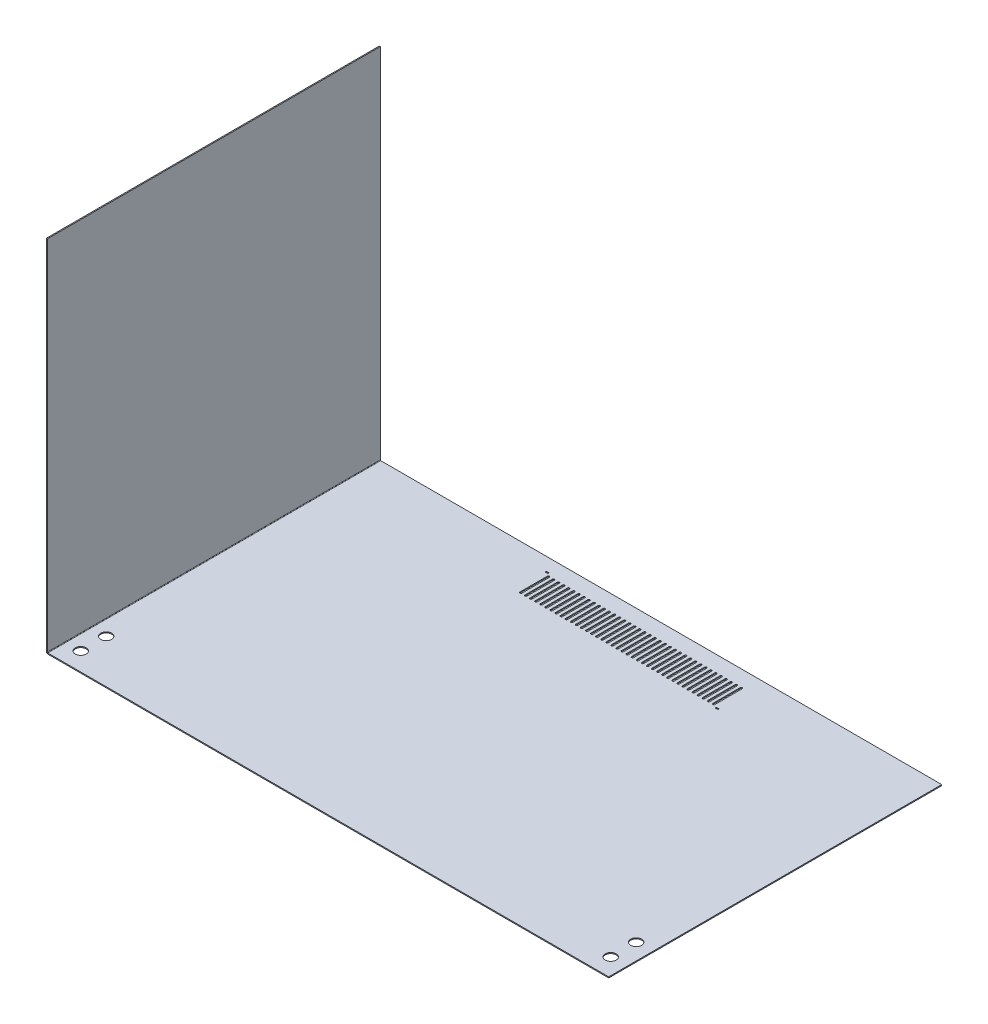
SolidWorks part; units mm, degrees
note: The reader was unsure of these and kept them because the rebuilt part matched: flange length of "Ребро-кромка1".
ref_plane "Спереди" through (0, 0, 0) normal (0, 0, 1) x (1, 0, 0)
ref_plane "Сверху" through (0, 0, 0) normal (0, 1, 0) x (1, 0, 0)
ref_plane "Справа" through (0, 0, 0) normal (1, 0, 0) x (0, 0, -1)
sketch "Эскиз1" plane through (0, 0, 0) normal (0, 1, 0) x (1, 0, 0)
  line L1 (0, 0) -> (1108, 0)
  line L2 (0, 0) -> (0, 656)
  line L3 (0, 656) -> (1108, 656)
  line L4 (1108, 0) -> (1108, 656)
  dimension "D1" = 656
  dimension "D2" = 1108
base flange "Базовая кромка1" sketch "Эскиз1" thickness 2 reverse thickness direction no parameters "D1"=1
edge flange "Ребро-кромка1" sketch "Эскиз19" flange angle 90 flange length 708 flange position material inside bend radius 1 thickness 2 relief rectangular parameters "D6"=10
bend "EdgeBend5" bend radius 1 bend angle 90 parameters "D5"=1
sketch "Эскиз19" plane through (0, 0, 0) normal (-1, 0, 0) x (0, 0, 1)
  line L0 (-656, 0) -> (0, 0) construction
  line L1 (-656, 0) -> (0, 0)
  line L2 (-656, 0) -> (-656, 706)
  line L3 (-656, 706) -> (0, 706)
  line L4 (0, 706) -> (0, 0)
sketch "Эскиз21" plane through (0, -2, 0) normal (0, -1, 0) x (1, 0, 0)
  line L0 (554, 0) -> (554, -656) construction
  line L1 (0, 0) -> (1108, 0) construction
  line L2 (1108, -656) -> (3, -656) construction
  line L3 (0, 0) -> (0, -656) construction
  line L4 (3, 0) -> (1108, 0) construction
  line L5 (746, -623) -> (746, -569) construction
  line L10 (744, -623) -> (744, -569)
  line L11 (748, -623) -> (748, -569)
  line L12 (554, -626) -> (554, -566) construction
  line L13 (746, -566) -> (362, -566) construction
  line L14 (749, -569) -> (749, -623) construction
  line L15 (746, -626) -> (362, -626) construction
  line L16 (359, -569) -> (359, -623) construction
  line L17 (736, -623) -> (736, -569) construction
  line L18 (734, -623) -> (734, -569)
  line L19 (738, -623) -> (738, -569)
  line L20 (726, -623) -> (726, -569) construction
  line L21 (724, -623) -> (724, -569)
  line L22 (728, -623) -> (728, -569)
  line L23 (716, -623) -> (716, -569) construction
  line L24 (714, -623) -> (714, -569)
  line L25 (718, -623) -> (718, -569)
  line L26 (706, -623) -> (706, -569) construction
  line L27 (704, -623) -> (704, -569)
  line L28 (708, -623) -> (708, -569)
  line L29 (696, -623) -> (696, -569) construction
  line L30 (694, -623) -> (694, -569)
  line L31 (698, -623) -> (698, -569)
  line L32 (686, -623) -> (686, -569) construction
  line L33 (684, -623) -> (684, -569)
  line L34 (688, -623) -> (688, -569)
  line L35 (676, -623) -> (676, -569) construction
  line L36 (674, -623) -> (674, -569)
  line L37 (678, -623) -> (678, -569)
  line L38 (666, -623) -> (666, -569) construction
  line L39 (664, -623) -> (664, -569)
  line L40 (668, -623) -> (668, -569)
  line L41 (656, -623) -> (656, -569) construction
  line L42 (654, -623) -> (654, -569)
  line L43 (658, -623) -> (658, -569)
  line L44 (646, -623) -> (646, -569) construction
  line L45 (644, -623) -> (644, -569)
  line L46 (648, -623) -> (648, -569)
  line L47 (636, -623) -> (636, -569) construction
  line L48 (634, -623) -> (634, -569)
  line L49 (638, -623) -> (638, -569)
  line L50 (626, -623) -> (626, -569) construction
  line L51 (624, -623) -> (624, -569)
  line L52 (628, -623) -> (628, -569)
  line L53 (616, -623) -> (616, -569) construction
  line L54 (614, -623) -> (614, -569)
  line L55 (618, -623) -> (618, -569)
  line L56 (606, -623) -> (606, -569) construction
  line L57 (604, -623) -> (604, -569)
  line L58 (608, -623) -> (608, -569)
  line L59 (596, -623) -> (596, -569) construction
  line L60 (594, -623) -> (594, -569)
  line L61 (598, -623) -> (598, -569)
  line L62 (586, -623) -> (586, -569) construction
  line L63 (584, -623) -> (584, -569)
  line L64 (588, -623) -> (588, -569)
  line L65 (576, -623) -> (576, -569) construction
  line L66 (574, -623) -> (574, -569)
  line L67 (578, -623) -> (578, -569)
  line L68 (566, -623) -> (566, -569) construction
  line L69 (564, -623) -> (564, -569)
  line L70 (568, -623) -> (568, -569)
  line L71 (556, -623) -> (556, -569) construction
  line L72 (554, -623) -> (554, -569)
  line L73 (558, -623) -> (558, -569)
  line L74 (546, -623) -> (546, -569) construction
  line L75 (544, -623) -> (544, -569)
  line L76 (548, -623) -> (548, -569)
  line L77 (536, -623) -> (536, -569) construction
  line L78 (534, -623) -> (534, -569)
  line L79 (538, -623) -> (538, -569)
  line L80 (526, -623) -> (526, -569) construction
  line L81 (524, -623) -> (524, -569)
  line L82 (528, -623) -> (528, -569)
  line L83 (516, -623) -> (516, -569) construction
  line L84 (514, -623) -> (514, -569)
  line L85 (518, -623) -> (518, -569)
  line L86 (506, -623) -> (506, -569) construction
  line L87 (504, -623) -> (504, -569)
  line L88 (508, -623) -> (508, -569)
  line L89 (496, -623) -> (496, -569) construction
  line L90 (494, -623) -> (494, -569)
  line L91 (498, -623) -> (498, -569)
  line L92 (486, -623) -> (486, -569) construction
  line L93 (484, -623) -> (484, -569)
  line L94 (488, -623) -> (488, -569)
  line L95 (476, -623) -> (476, -569) construction
  line L96 (474, -623) -> (474, -569)
  line L97 (478, -623) -> (478, -569)
  line L98 (466, -623) -> (466, -569) construction
  line L99 (464, -623) -> (464, -569)
  line L100 (468, -623) -> (468, -569)
  line L101 (456, -623) -> (456, -569) construction
  line L102 (454, -623) -> (454, -569)
  line L103 (458, -623) -> (458, -569)
  line L104 (446, -623) -> (446, -569) construction
  line L105 (444, -623) -> (444, -569)
  line L106 (448, -623) -> (448, -569)
  line L107 (436, -623) -> (436, -569) construction
  line L108 (434, -623) -> (434, -569)
  line L109 (438, -623) -> (438, -569)
  line L110 (426, -623) -> (426, -569) construction
  line L111 (424, -623) -> (424, -569)
  line L112 (428, -623) -> (428, -569)
  line L113 (416, -623) -> (416, -569) construction
  line L114 (414, -623) -> (414, -569)
  line L115 (418, -623) -> (418, -569)
  line L116 (406, -623) -> (406, -569) construction
  line L117 (404, -623) -> (404, -569)
  line L118 (408, -623) -> (408, -569)
  line L119 (396, -623) -> (396, -569) construction
  line L120 (394, -623) -> (394, -569)
  line L121 (398, -623) -> (398, -569)
  line L122 (386, -623) -> (386, -569) construction
  line L123 (384, -623) -> (384, -569)
  line L124 (388, -623) -> (388, -569)
  line L125 (376, -623) -> (376, -569) construction
  line L126 (374, -623) -> (374, -569)
  line L127 (378, -623) -> (378, -569)
  line L128 (366, -623) -> (366, -569) construction
  line L129 (364, -623) -> (364, -569)
  line L130 (368, -623) -> (368, -569)
  line L131 (357.4991, -630.0926) -> (357.5514, -628.5935) construction
  line L132 (358.9982, -630.1449) -> (356, -630.0402) construction
  line L133 (356.0523, -628.5411) -> (359.0505, -628.6458) construction
  line L134 (356.0253, -629.2906) -> (359.0253, -629.3954) construction
  line L135 (356.0671, -628.0914) -> (359.0671, -628.1961)
  line L136 (355.9834, -630.4899) -> (358.9834, -630.5947)
  line L137 (756.9969, -565.4955) -> (757.0492, -563.9964) construction
  line L138 (758.4959, -565.5478) -> (755.4978, -565.4431) construction
  line L139 (755.5501, -563.944) -> (758.5483, -564.0487) construction
  line L140 (755.523, -564.6935) -> (758.523, -564.7983) construction
  line L141 (755.5649, -563.4943) -> (758.5649, -563.599)
  line L142 (755.4812, -565.8928) -> (758.4812, -565.9976)
  circle A0 centre (32, -36) radius 10.75
  circle A1 centre (32, -86) radius 10.75
  circle A2 centre (1076, -86) radius 10.75
  circle A3 centre (1076, -36) radius 10.75
  arc A10 (362, -566) -> (359, -569) centre (362, -569) ccw construction
  arc A11 (359, -623) -> (362, -626) centre (362, -623) ccw construction
  arc A12 (746, -626) -> (749, -623) centre (746, -623) ccw construction
  arc A13 (749, -569) -> (746, -566) centre (746, -569) ccw construction
  arc A14 (744, -623) -> (748, -623) centre (746, -623) ccw
  arc A15 (748, -569) -> (744, -569) centre (746, -569) ccw
  arc A16 (734, -623) -> (738, -623) centre (736, -623) ccw
  arc A17 (738, -569) -> (734, -569) centre (736, -569) ccw
  arc A18 (724, -623) -> (728, -623) centre (726, -623) ccw
  arc A19 (728, -569) -> (724, -569) centre (726, -569) ccw
  arc A20 (714, -623) -> (718, -623) centre (716, -623) ccw
  arc A21 (718, -569) -> (714, -569) centre (716, -569) ccw
  arc A22 (704, -623) -> (708, -623) centre (706, -623) ccw
  arc A23 (708, -569) -> (704, -569) centre (706, -569) ccw
  arc A24 (694, -623) -> (698, -623) centre (696, -623) ccw
  arc A25 (698, -569) -> (694, -569) centre (696, -569) ccw
  arc A26 (684, -623) -> (688, -623) centre (686, -623) ccw
  arc A27 (688, -569) -> (684, -569) centre (686, -569) ccw
  arc A28 (674, -623) -> (678, -623) centre (676, -623) ccw
  arc A29 (678, -569) -> (674, -569) centre (676, -569) ccw
  arc A30 (664, -623) -> (668, -623) centre (666, -623) ccw
  arc A31 (668, -569) -> (664, -569) centre (666, -569) ccw
  arc A32 (654, -623) -> (658, -623) centre (656, -623) ccw
  arc A33 (658, -569) -> (654, -569) centre (656, -569) ccw
  arc A34 (644, -623) -> (648, -623) centre (646, -623) ccw
  arc A35 (648, -569) -> (644, -569) centre (646, -569) ccw
  arc A36 (634, -623) -> (638, -623) centre (636, -623) ccw
  arc A37 (638, -569) -> (634, -569) centre (636, -569) ccw
  arc A38 (624, -623) -> (628, -623) centre (626, -623) ccw
  arc A39 (628, -569) -> (624, -569) centre (626, -569) ccw
  arc A40 (614, -623) -> (618, -623) centre (616, -623) ccw
  arc A41 (618, -569) -> (614, -569) centre (616, -569) ccw
  arc A42 (604, -623) -> (608, -623) centre (606, -623) ccw
  arc A43 (608, -569) -> (604, -569) centre (606, -569) ccw
  arc A44 (594, -623) -> (598, -623) centre (596, -623) ccw
  arc A45 (598, -569) -> (594, -569) centre (596, -569) ccw
  arc A46 (584, -623) -> (588, -623) centre (586, -623) ccw
  arc A47 (588, -569) -> (584, -569) centre (586, -569) ccw
  arc A48 (574, -623) -> (578, -623) centre (576, -623) ccw
  arc A49 (578, -569) -> (574, -569) centre (576, -569) ccw
  arc A50 (564, -623) -> (568, -623) centre (566, -623) ccw
  arc A51 (568, -569) -> (564, -569) centre (566, -569) ccw
  arc A52 (554, -623) -> (558, -623) centre (556, -623) ccw
  arc A53 (558, -569) -> (554, -569) centre (556, -569) ccw
  arc A54 (544, -623) -> (548, -623) centre (546, -623) ccw
  arc A55 (548, -569) -> (544, -569) centre (546, -569) ccw
  arc A56 (534, -623) -> (538, -623) centre (536, -623) ccw
  arc A57 (538, -569) -> (534, -569) centre (536, -569) ccw
  arc A58 (524, -623) -> (528, -623) centre (526, -623) ccw
  arc A59 (528, -569) -> (524, -569) centre (526, -569) ccw
  arc A60 (514, -623) -> (518, -623) centre (516, -623) ccw
  arc A61 (518, -569) -> (514, -569) centre (516, -569) ccw
  arc A62 (504, -623) -> (508, -623) centre (506, -623) ccw
  arc A63 (508, -569) -> (504, -569) centre (506, -569) ccw
  arc A64 (494, -623) -> (498, -623) centre (496, -623) ccw
  arc A65 (498, -569) -> (494, -569) centre (496, -569) ccw
  arc A66 (484, -623) -> (488, -623) centre (486, -623) ccw
  arc A67 (488, -569) -> (484, -569) centre (486, -569) ccw
  arc A68 (474, -623) -> (478, -623) centre (476, -623) ccw
  arc A69 (478, -569) -> (474, -569) centre (476, -569) ccw
  arc A70 (464, -623) -> (468, -623) centre (466, -623) ccw
  arc A71 (468, -569) -> (464, -569) centre (466, -569) ccw
  arc A72 (454, -623) -> (458, -623) centre (456, -623) ccw
  arc A73 (458, -569) -> (454, -569) centre (456, -569) ccw
  arc A74 (444, -623) -> (448, -623) centre (446, -623) ccw
  arc A75 (448, -569) -> (444, -569) centre (446, -569) ccw
  arc A76 (434, -623) -> (438, -623) centre (436, -623) ccw
  arc A77 (438, -569) -> (434, -569) centre (436, -569) ccw
  arc A78 (424, -623) -> (428, -623) centre (426, -623) ccw
  arc A79 (428, -569) -> (424, -569) centre (426, -569) ccw
  arc A80 (414, -623) -> (418, -623) centre (416, -623) ccw
  arc A81 (418, -569) -> (414, -569) centre (416, -569) ccw
  arc A82 (404, -623) -> (408, -623) centre (406, -623) ccw
  arc A83 (408, -569) -> (404, -569) centre (406, -569) ccw
  arc A84 (394, -623) -> (398, -623) centre (396, -623) ccw
  arc A85 (398, -569) -> (394, -569) centre (396, -569) ccw
  arc A86 (384, -623) -> (388, -623) centre (386, -623) ccw
  arc A87 (388, -569) -> (384, -569) centre (386, -569) ccw
  arc A88 (374, -623) -> (378, -623) centre (376, -623) ccw
  arc A89 (378, -569) -> (374, -569) centre (376, -569) ccw
  arc A90 (364, -623) -> (368, -623) centre (366, -623) ccw
  arc A91 (368, -569) -> (364, -569) centre (366, -569) ccw
  arc A92 (356.0671, -628.0914) -> (355.9834, -630.4899) centre (356.0253, -629.2906) ccw
  arc A93 (358.9834, -630.5947) -> (359.0671, -628.1961) centre (359.0253, -629.3954) ccw
  arc A94 (755.5649, -563.4943) -> (755.4812, -565.8928) centre (755.523, -564.6935) ccw
  arc A95 (758.4812, -565.9976) -> (758.5649, -563.599) centre (758.523, -564.7983) ccw
  point P20 (359, -566)
  point P24 (359, -626)
  point P28 (749, -626)
  point P33 (746, -596)
  point P40 (736, -596)
  point P50 (726, -596)
  point P57 (716, -596)
  point P64 (706, -596)
  point P71 (696, -596)
  point P78 (686, -596)
  point P85 (676, -596)
  point P92 (666, -596)
  point P99 (656, -596)
  point P106 (646, -596)
  point P113 (636, -596)
  point P120 (626, -596)
  point P127 (616, -596)
  point P134 (606, -596)
  point P141 (596, -596)
  point P148 (586, -596)
  point P155 (576, -596)
  point P162 (566, -596)
  point P169 (556, -596)
  point P176 (546, -596)
  point P183 (536, -596)
  point P190 (526, -596)
  point P197 (516, -596)
  point P204 (506, -596)
  point P211 (496, -596)
  point P218 (486, -596)
  point P225 (476, -596)
  point P232 (466, -596)
  point P239 (456, -596)
  point P246 (446, -596)
  point P253 (436, -596)
  point P260 (426, -596)
  point P267 (416, -596)
  point P274 (406, -596)
  point P281 (396, -596)
  point P288 (386, -596)
  point P295 (376, -596)
  point P302 (366, -596)
  point P314 (357.5253, -629.343)
  point P327 (757.023, -564.7459)
  dimension "D1" = 21.5
  dimension "D3" = 36
  dimension "D5" = 3
  dimension "D7" = 2
  dimension "D11" = 1.2
  dimension "D13" = 1.2
  dimension "D2" = 32
  dimension "D6" = 30
  dimension "D8" = 390
  dimension "D9" = 60
  dimension "D12" = 3
  dimension "D14" = 3
  dimension "D4" = 2
  dimension "D10" = 39
extrude "Вырез-Вытянуть2" cut sketch "Эскиз21" against normal blind 2 normal cut yes
sketch "Сгиб-Линии1" [suppressed] plane through (0, 0, 0) normal (0, 1, 0) x (1, 0, 0)
sketch "Граничная рамка1" [suppressed] plane through (0, 0, 0) normal (0, 1, 0) x (1, 0, 0)
sheet metal parameters "Листовой металл3" thickness 2 parameters "D1"=1
flat pattern "Развертка3" [suppressed]
sketch "Сгиб-Линии2" plane through (0, 0, 0) normal (0, 1, 0) x (1, 0, 0)
sketch "Граничная рамка2" [suppressed] plane through (0, 0, 0) normal (0, 1, 0) x (1, 0, 0)
sheet metal parameters "Листовой металл4" thickness 2 parameters "D1"=1
flat pattern "Развертка3" [suppressed]
sketch "Сгиб-Линии2" plane through (0, 0, 0) normal (0, 1, 0) x (1, 0, 0)
sketch "Граничная рамка2" [suppressed] plane through (0, 0, 0) normal (0, 1, 0) x (1, 0, 0)
bend of the flat pattern "Плоское состояние-<EdgeBend5>1"
sheet metal parameters "Листовой металл8" thickness 2 parameters "D1"=1
flat pattern "Развертка3"
sketch "Сгиб-Линии2" plane through (0, 0, 0) normal (0, 1, 0) x (1, 0, 0)
  line L0 (1.5077, 656) -> (1.5077, 0) construction
  line L1 (1.5077, 656) -> (1.5077, 0) construction
sketch3d "Граничная рамка2" [suppressed]
  line L0 (1108, 656, 0) -> (-704.9845, 656, 0) construction
  line L1 (1108, 0, 0) -> (-704.9845, 0, 0) construction
  line L2 (1108, 656, 0) -> (1108, 0, 0) construction
  line L3 (-704.9845, 656, 0) -> (-704.9845, 0, 0) construction
bend of the flat pattern "Плоское состояние-<EdgeBend5>1"
